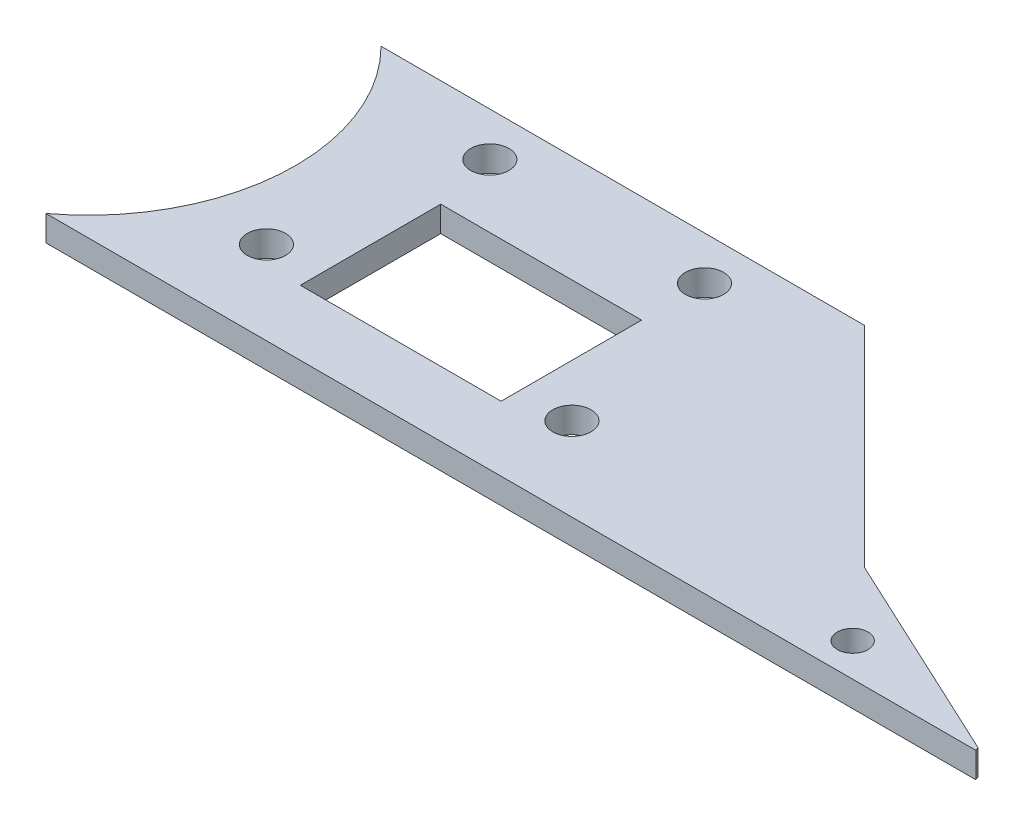
SolidWorks part; units mm, degrees
ref_plane "Спереди" through (0, 0, 0) normal (0, 0, 1) x (1, 0, 0)
ref_plane "Сверху" through (0, 0, 0) normal (0, 1, 0) x (1, 0, 0)
ref_plane "Справа" through (0, 0, 0) normal (1, 0, 0) x (0, 0, -1)
sketch "Эскиз1" plane through (0, 0, 0) normal (0, 1, 0) x (1, 0, 0)
  line L13 (-56.9238, -23.832) -> (16.3829, -23.832)
  line L14 (16.3829, -23.832) -> (-0.8369, -15.8022)
  line L15 (-0.8369, -15.8022) -> (-17.272, 0.6328)
  line L20 (-36.2092, 0.6328) -> (-36.2092, -23.832) construction
  line L25 (-26.3662, -7.7426) -> (-42.0968, -7.7426)
  line L28 (-55.1464, 0.6328) -> (-17.272, 0.6328)
  line L29 (-26.3662, -7.7426) -> (-26.3662, -18.7426)
  line L30 (-26.3662, -18.7426) -> (-42.0968, -18.7426)
  line L31 (-42.0968, -7.7426) -> (-42.0968, -18.7426)
  arc A1 (-51.7409, -17.2996) -> (-55.1464, 0.6328) centre (-66.6008, -10.832) ccw
  arc A2 (-56.9238, -23.832) -> (-51.7409, -17.2996) centre (-66.6008, -10.832) ccw
  circle A3 centre (-43.2057, -2.7898) radius 1.5
  circle A4 centre (-26.393, -2.7898) radius 1.5
  circle A5 centre (-46.1933, -17.2996) radius 1.5
  circle A6 centre (-22.2662, -17.2996) radius 1.5
  dimension "D1" = 15.7306
  dimension "D6" = 4.1
  dimension "D2" = 11
  dimension "D3" = 5.0894
  dimension "D4" = 6.5324
  dimension "D5" = 4.0965
  dimension "D7" = 24.4648
  dimension "D8" = 9.843
extrude "Бобышка-Вытянуть1" add sketch "Эскиз1" along normal blind 2
sketch "Эскиз2" plane through (0, 2, 0) normal (0, 1, 0) x (1, 0, 0)
  line L0 (16.3829, -23.832) -> (15.8003, -23.5603)
  line L1 (16.3829, -23.832) -> (-0.8369, -15.8022) construction
  line L2 (15.4155, -22.503) -> (15.8992, -23.832) construction
  line L3 (15.8003, -23.5603) -> (15.8992, -23.832)
  line L4 (15.8992, -23.832) -> (-0.4143, -16.2248) construction
  line L5 (15.8992, -23.832) -> (16.3829, -23.832)
extrude "Вырез-Вытянуть1" cut sketch "Эскиз2" against normal through all and the other way blind 106.5
sketch "Эскиз5" plane through (0, 2, 0) normal (0, -1, 0) x (1, 0, 0)
  circle A0 centre (-22.2662, 17.2996) radius 1.5
sketch "Эскиз6" plane through (0, 2, 0) normal (0, -1, 0) x (1, 0, 0)
  circle A0 centre (-22.2662, 17.2996) radius 1.5
sketch "Эскиз7" plane through (0, 0, 0) normal (0, -1, 0) x (1, 0, 0)
  line L2 (-0.8369, 21.2247) -> (12.3982, 21.2247) construction
  circle A0 centre (3.6511, 21.2247) radius 1.2
extrude "Вырез-Вытянуть5" cut sketch "Эскиз7" against normal blind 15
sketch "Эскиз8" plane through (0, 2, 0) normal (0, -1, 0) x (1, 0, 0)
  circle A0 centre (3.6511, 21.2247) radius 1.5
